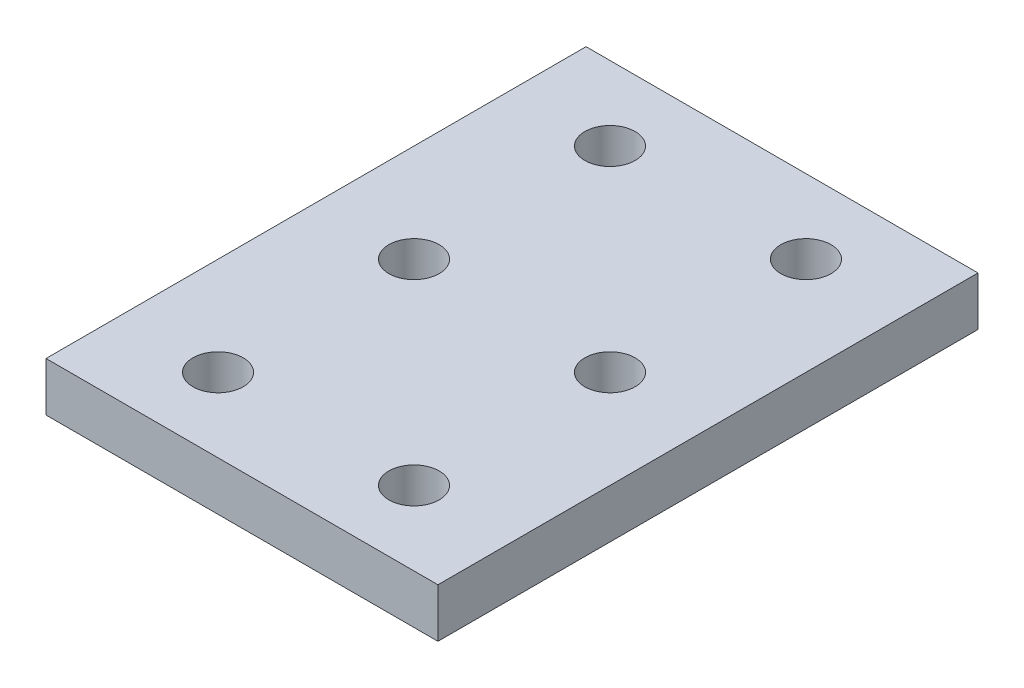
SolidWorks part; units mm, degrees
other "DetailItem2"
material "AISI 316 Stainless Steel Sheet (SS)"
ref_plane "Front Plane" through (0, 0, 0) normal (0, 0, 1) x (1, 0, 0)
ref_plane "Top Plane" through (0, 0, 0) normal (0, 1, 0) x (1, 0, 0)
ref_plane "Right Plane" through (0, 0, 0) normal (1, 0, 0) x (0, 0, -1)
ref_plane "40K Bottom Cold head Location" through (0, 236.49, 0) normal (0, 1, 0) x (1, 0, 0)
sketch "Sketch1" plane through (0, 0, 0) normal (0, 1, 0) x (1, 0, 0)
  line L0 (62.5, -17.5) -> (37.1, -17.5)
  line L5 (37.1, 17.5) -> (62.5, 17.5)
  line L6 (37.1, 17.5) -> (37.1, -17.5)
  line L8 (62.5, 17.5) -> (62.5, -17.5)
  circle A0 centre (43.45, 0) radius 1.63
  circle A6 centre (56.15, 0) radius 1.63
  circle A7 centre (43.45, 12.7) radius 1.63
  circle A8 centre (56.15, 12.7) radius 1.63
  circle A9 centre (43.45, -12.7) radius 1.63
  circle A10 centre (56.15, -12.7) radius 1.63
  point P6 (37.1, 0)
  dimension "D5" = 3.26
  dimension "D1" = 25.4
  dimension "D2" = 35
  dimension "D10" = 37.1
  dimension "D11" = 17.5
  dimension "D3" = 6.35
  dimension "D8" = 12.7
  dimension "D9" = 12.7
  dimension "D4" = 6.35
ref_plane "Top_Connection_Plane" through (22.5, 0, 0) normal (1, 0, 0) x (0, 0, -1)
ref_plane "Bottom_Connection_Plane" through (58, 0, 0) normal (1, 0, 0) x (0, 0, -1)
extrude "Boss-Extrude2" add sketch "Sketch1" along normal blind 3.175 separate body contours L6 L0 L5 A10 A8 A0 | L0 | L8 L5 L0 | L5 region at (49.8, 0, 0)
equation "\"Distance_From_Cold_Center\"=37.1"
equation "\"D10@Sketch1\"=\"Distance_From_Cold_Center\""
equation "\"D11@Sketch1\"=\"D2@Sketch1\"/2"
equation "\"Inside_Cold_Rod_Dia\"=52"
equation "\"40K_Cold_Head_Dia\"=45"
equation "\"D8@Sketch2\"=\"40K_Cold_Head_Dia\""
